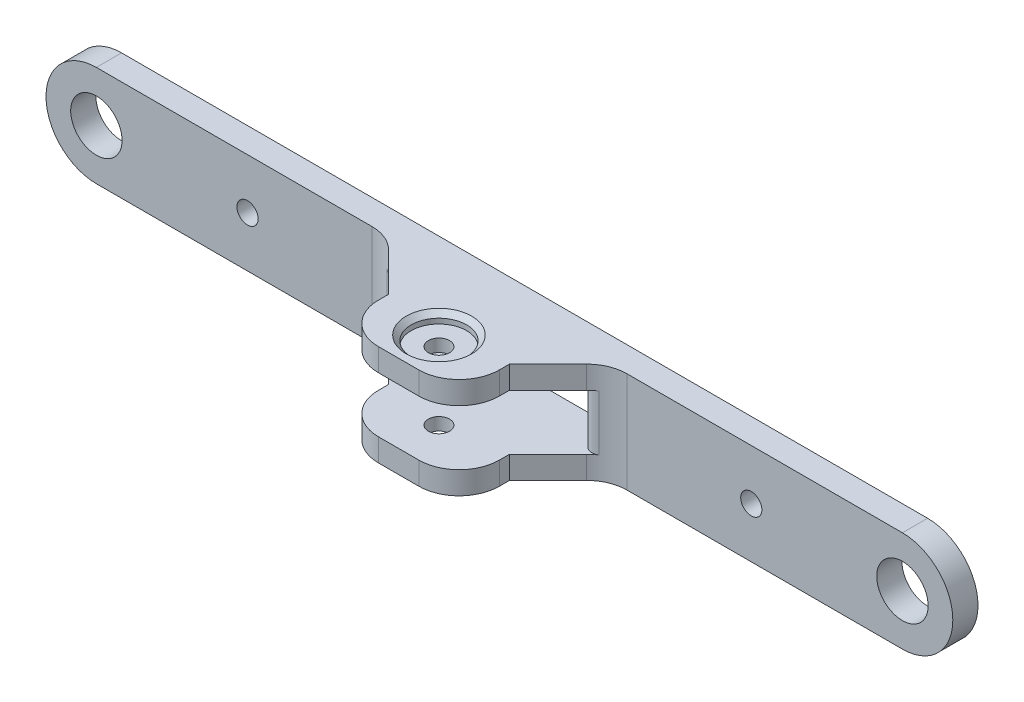
SolidWorks part; units mm, degrees
ref_plane "Plan de face" through (0, 0, 0) normal (0, 0, 1) x (1, 0, 0)
ref_plane "Plan de dessus" through (0, 0, 0) normal (0, 1, 0) x (1, 0, 0)
ref_plane "Plan de droite" through (0, 0, 0) normal (1, 0, 0) x (0, 0, -1)
sketch "Esquisse1" plane through (0, 0, 0) normal (0, 0, 1) x (1, 0, 0)
  line L0 (-80, 0) -> (80, 0) construction
  line L1 (-80, 10) -> (80, 10)
  line L2 (-80, -10) -> (80, -10)
  arc A0 (-80, 10) -> (-80, -10) centre (-80, 0) ccw
  arc A1 (80, -10) -> (80, 10) centre (80, 0) ccw
  point P3 (0, 0)
  dimension "D1" = 160
  dimension "D2" = 20
  dimension "D3" = 80
extrude "Boss.-Extru.1" add sketch "Esquisse1" along normal blind 5
sketch "Esquisse2" plane through (0, 0, 5) normal (0, 0, 1) x (1, 0, 0)
  line L0 (80, 10) -> (-80, 10) construction
  circle A0 centre (-80, 0) radius 5.1
  circle A1 centre (80, 0) radius 5.1
  arc A2 (-80, 10) -> (-80, -10) centre (-80, 0) ccw construction
  arc A3 (80, -10) -> (80, 10) centre (80, 0) ccw construction
  circle A4 centre (-50, 0) radius 2.1
  circle A5 centre (50, 0) radius 2.1
  dimension "D1" = 10.2
  dimension "D2" = 10.2
  dimension "D3" = 4.2
  dimension "D4" = 4.2
  dimension "D5" = 100
  dimension "D6" = 50
  dimension "D7" = 10
  dimension "D8" = 10
extrude "Enlèv. mat.-Extru.1" cut sketch "Esquisse2" against normal through all
sketch "Esquisse3" plane through (0, 0, 5) normal (0, 0, 1) x (1, 0, 0)
  line L0 (80, 10) -> (-80, 10) construction
  line L1 (-12, 10) -> (12, 10)
  line L2 (-12, 10) -> (-12, -10)
  line L3 (-12, -10) -> (12, -10)
  line L4 (12, 10) -> (12, -10)
  line L5 (-80, -10) -> (80, -10) construction
  dimension "D1" = 24
  dimension "D2" = 12
extrude "Boss.-Extru.2" add sketch "Esquisse3" along normal blind 20
chamfer "Chanfrein1" distance 10 angle 45 2 edges
sketch "Esquisse4" plane through (0, 0, 25) normal (0, 0, 1) x (1, 0, 0)
  line L0 (12, 10) -> (-12, 10) construction
  line L1 (-18, 5.5) -> (18, 5.5)
  line L2 (-18, 5.5) -> (-18, -5.5)
  line L3 (-18, -5.5) -> (18, -5.5)
  line L4 (18, 5.5) -> (18, -5.5)
  line L5 (-12, 10) -> (-12, -10) construction
  line L6 (12, -10) -> (12, 10) construction
  dimension "D1" = 11
  dimension "D2" = 4.5
  dimension "D3" = 6
  dimension "D4" = 6
extrude "Enlèv. mat.-Extru.2" cut sketch "Esquisse4" against normal blind 20
sketch "Esquisse5" plane through (0, 10, 0) normal (0, 1, 0) x (1, 0, 0)
  line L0 (12, -25) -> (-12, -25) construction
  line L1 (-12, -25) -> (-12, -15) construction
  circle A0 centre (0, -17) radius 2.1
  dimension "D1" = 4.2
  dimension "D2" = 8
  dimension "D3" = 12
extrude "Enlèv. mat.-Extru.3" cut sketch "Esquisse5" against normal through all
fillet "Congé1" radius 8 6 edges at (-22, 0, 5) (-12, -7.75, 25) (12, -7.75, 25) (22, 0, 5) (-12, 7.75, 25) (12, 7.75, 25)
sketch "Esquisse6" plane through (0, 10, 0) normal (0, 1, 0) x (1, 0, 0)
  circle A0 centre (0, -17) radius 5.5
  dimension "D1" = 11
extrude "Enlèv. mat.-Extru.4" cut sketch "Esquisse6" against normal blind 2
chamfer "Chanfrein2" distance 1 angle 45 1 edges at (0, 10, 22.5)
fillet "Congé4" radius 2 2 edges at (18, 0, 9) (-18, 0, 9)
sketch "Esquisse7" plane through (0, -10, 0) normal (0, -1, 0) x (1, 0, 0)
  circle A0 centre (0, 17) radius 5.5
  dimension "D1" = 11
extrude "Enlèv. mat.-Extru.5" cut sketch "Esquisse7" against normal blind 2
chamfer "Chanfrein3" distance 1 angle 45 1 edges at (0, -10, 11.5)
sketch "Esquisse8" plane through (0, 0, 5) normal (0, 0, 1) x (1, 0, 0)
  line L1 (-18, -5.5) -> (18, -5.5)
  line L2 (-18, -5.5) -> (-18, 5.5)
  line L3 (-18, 5.5) -> (18, 5.5)
  line L4 (18, -5.5) -> (18, 5.5)
extrude "Enlèv. mat.-Extru.6" cut sketch "Esquisse8" against normal through all
sketch "Esquisse9" plane through (0, -10, 0) normal (0, -1, 0) x (1, 0, 0)
  line L0 (-80, 0) -> (80, 0) construction
  line L1 (-1, 0) -> (1, 0)
  line L2 (-1, 0) -> (-1, 5)
  line L3 (-1, 5) -> (1, 5)
  line L4 (1, 0) -> (1, 5)
  point P6 (0, 0)
  dimension "D1" = 2
  dimension "D2" = 1
  dimension "D3" = 5
extrude "Enlèv. mat.-Extru.7" cut sketch "Esquisse9" against normal blind 2
